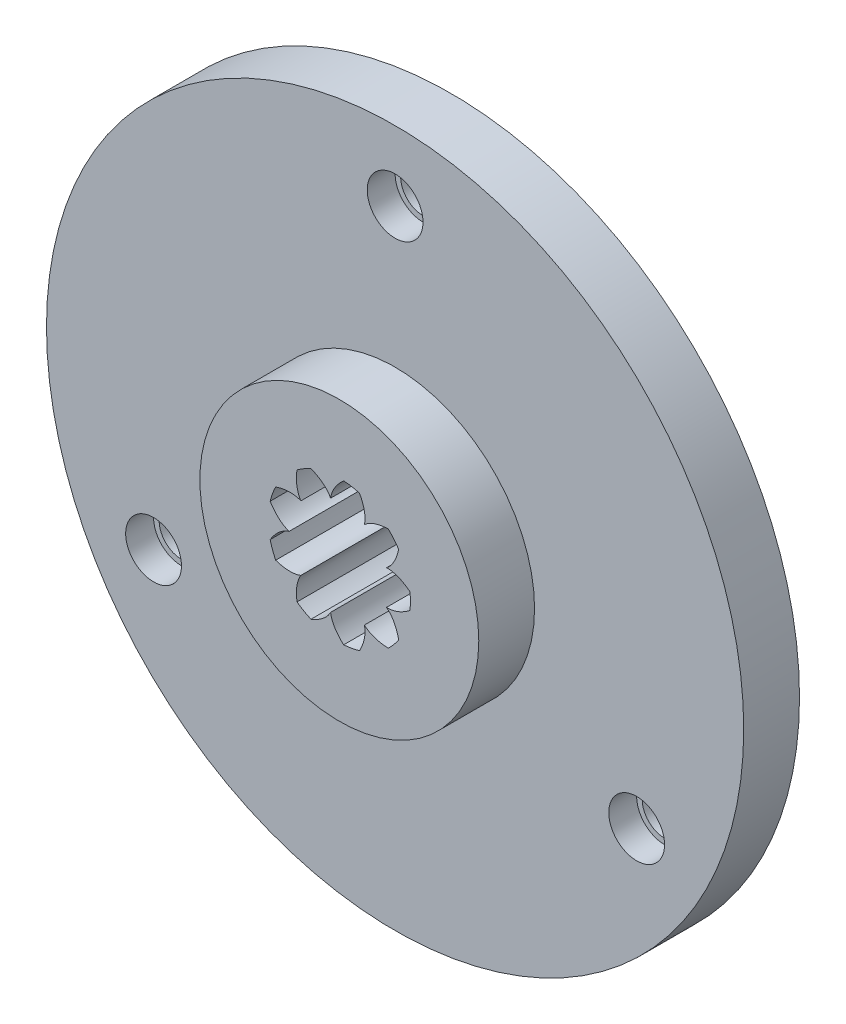
SolidWorks part; units mm, degrees
ref_plane "前视基准面" through (0, 0, 0) normal (0, 0, 1) x (1, 0, 0)
ref_plane "上视基准面" through (0, 0, 0) normal (0, 1, 0) x (1, 0, 0)
ref_plane "右视基准面" through (0, 0, 0) normal (1, 0, 0) x (0, 0, -1)
other "Configuration Table"
sketch "草图1" plane through (0, 0, 0) normal (0, 0, 1) x (1, 0, 0)
  line L0 (0, 0) -> (1.6914, 0.6156) construction
  line L1 (0, 0) -> (1.5832, 0.5954)
  line L2 (0, 0) -> (1.5832, -0.5954)
  line L3 (0, 0) -> (1.6914, -0.6156) construction
  line L4 (0, 0) -> (2.55, 0) construction
  line L5 (1.6914, 0.6156) -> (1.6914, -0.6156) construction
  circle A0 centre (0, 0) radius 1.65
  circle A1 centre (0, 0) radius 2.55
  circle A2 centre (0, 0) radius 1.6914 construction
  circle A3 centre (0, 0) radius 1.8 construction
  circle A4 centre (0, 0) radius 3
  spline S0 degree 4 poles (1.5832, 0.5954) (1.5953, 0.5999) (1.6299, 0.61) (1.6985, 0.6188) (1.8107, 0.6176) (1.9542, 0.5935) (2.1323, 0.5368) (2.3288, 0.4397) (2.527, 0.3033) (2.7182, 0.1281) (2.8863, -0.0692) (3.0309, -0.2841) (3.1583, -0.5243) (3.284, -0.8365) (3.3855, -1.2255) (3.4358, -1.6902) (3.4119, -2.2085) (3.3126, -2.7182) (3.1474, -3.2089) (2.918, -3.6756) (2.6387, -4.1089) (2.3029, -4.5102) (1.9385, -4.866) (1.5141, -5.1906) (1.1742, -5.4065) (0.7714, -5.6132) (0.5343, -5.7151) (0.2601, -5.8236) (0.1183, -5.8645) (-0.005, -5.9055) (-0.0434, -5.9147) (-0.0704, -5.9226) (-0.0848, -5.927) knots 0 0 0 0 0 0.005604 0.015718 0.02996 0.048734 0.068727 0.096889 0.125051 0.153212 0.181374 0.209535 0.237696 0.271429 0.327752 0.384075 0.440398 0.496721 0.553044 0.609367 0.66569 0.722013 0.778336 0.834659 0.890982 0.909091 0.954545 0.977273 0.988636 0.994318 1 1 1 1 1 construction
  spline S1 degree 4 poles (1.5832, 0.5954) (1.5953, 0.5999) (1.6299, 0.61) (1.6985, 0.6188) (1.8107, 0.6176) (1.9542, 0.5935) (2.1323, 0.5368) (2.3288, 0.4397) (2.527, 0.3033) (2.7182, 0.1281) (2.8863, -0.0692) (3.0309, -0.2841) (3.1583, -0.5243) (3.284, -0.8365) (3.3855, -1.2255) (3.4358, -1.6902) (3.4119, -2.2085) (3.3126, -2.7182) (3.1474, -3.2089) (2.918, -3.6756) (2.6387, -4.1089) (2.3029, -4.5102) (1.9385, -4.866) (1.5141, -5.1906) (1.1742, -5.4065) (0.8753, -5.5599) (0.734, -5.626) (0.6996, -5.6416) knots 0 0 0 0 0 0.005604 0.015718 0.02996 0.048734 0.068727 0.096889 0.125051 0.153212 0.181374 0.209535 0.237696 0.271429 0.327752 0.384075 0.440398 0.496721 0.553044 0.609367 0.66569 0.722013 0.778336 0.834659 0.890982 0.909091 0.909091 0.909091 0.909091 0.909091
  spline S2 degree 4 poles (1.5832, -0.5954) (1.5953, -0.5999) (1.6299, -0.61) (1.6985, -0.6188) (1.8107, -0.6176) (1.9542, -0.5935) (2.1323, -0.5368) (2.3288, -0.4397) (2.527, -0.3033) (2.7182, -0.1281) (2.8863, 0.0692) (3.0309, 0.2841) (3.1583, 0.5243) (3.284, 0.8365) (3.3855, 1.2255) (3.4358, 1.6902) (3.4119, 2.2085) (3.3126, 2.7182) (3.1474, 3.2089) (2.918, 3.6756) (2.6387, 4.1089) (2.3029, 4.5102) (1.9385, 4.866) (1.5141, 5.1906) (1.1742, 5.4065) (0.7714, 5.6132) (0.5343, 5.7151) (0.2601, 5.8236) (0.1183, 5.8645) (-0.005, 5.9055) (-0.0434, 5.9147) (-0.0704, 5.9226) (-0.0848, 5.927) knots 0 0 0 0 0 0.005604 0.015718 0.02996 0.048734 0.068727 0.096889 0.125051 0.153212 0.181374 0.209535 0.237696 0.271429 0.327752 0.384075 0.440398 0.496721 0.553044 0.609367 0.66569 0.722013 0.778336 0.834659 0.890982 0.909091 0.954545 0.977273 0.988636 0.994318 1 1 1 1 1 construction
  spline S3 degree 4 poles (1.5832, -0.5954) (1.5953, -0.5999) (1.6299, -0.61) (1.6985, -0.6188) (1.8107, -0.6176) (1.9542, -0.5935) (2.1323, -0.5368) (2.3288, -0.4397) (2.527, -0.3033) (2.7182, -0.1281) (2.8863, 0.0692) (3.0309, 0.2841) (3.1583, 0.5243) (3.284, 0.8365) (3.3855, 1.2255) (3.4358, 1.6902) (3.4119, 2.2085) (3.3126, 2.7182) (3.1474, 3.2089) (2.918, 3.6756) (2.6387, 4.1089) (2.3029, 4.5102) (1.9385, 4.866) (1.5141, 5.1906) (1.1742, 5.4065) (0.8753, 5.5599) (0.734, 5.626) (0.6996, 5.6416) knots 0 0 0 0 0 0.005604 0.015718 0.02996 0.048734 0.068727 0.096889 0.125051 0.153212 0.181374 0.209535 0.237696 0.271429 0.327752 0.384075 0.440398 0.496721 0.553044 0.609367 0.66569 0.722013 0.778336 0.834659 0.890982 0.909091 0.909091 0.909091 0.909091 0.909091
  point P16 (1.6914, 0)
  dimension "内啮合齿顶圆直径" = 3.3
  dimension "内啮合分度圆直径" = 3.6
  dimension "内啮合基圆直径" = 3.3829
  dimension "内啮合齿根圆直径" = 5.1
  dimension "外径" = 6
  dimension "渐开线镜像线夹角" = 20
extrude "凸台-拉伸1" add sketch "草图1" along normal blind 4 contours A4 | A0
extrude "切除-拉伸2" cut sketch "草图1<3>" along normal through all contours A0 S3 A1 S1 region at (2.0287, 0, 0)
sketch "草图1<3>" plane through (0, 0, 0) normal (0, 0, 1) x (1, 0, 0) same geometry as "草图1"
pattern_circular "阵列(圆周)1" count 9 over 360 about axis through (0, 0, 4) along (0, 0, 1) of "切除-拉伸2"
sketch "草图2" plane through (0, 0, 0) normal (0, 0, -1) x (-1, 0, 0)
  circle A0 centre (0, 0) radius 3
  circle A1 centre (0, 0) radius 3 construction
  circle A2 centre (0, 0) radius 5
  dimension "D1" = 10
extrude "凸台-拉伸2" add sketch "草图2" against normal up to surface (4 mm away) contours A2 | A0 up to face at (3, 0, 4)
sketch "草图3" plane through (0, 0, 0) normal (0, 0, 1) x (1, 0, 0)
  circle A0 centre (0, 10) radius 1
  circle A1 centre (0, 10) radius 0.8
  circle A2 centre (0, 0) radius 12.5
  circle A3 centre (8.6603, -5) radius 0.8
  circle A4 centre (8.6603, -5) radius 1
  circle A5 centre (-8.6603, -5) radius 0.8
  circle A6 centre (-8.6603, -5) radius 1
  circle A7 centre (0, 0) radius 5
  circle A10 centre (0, 0) radius 5 construction
  point P14 (0, 0)
  dimension "D4" = 1.6
  dimension "D5" = 2
  dimension "D1" = 25
  dimension "D2" = 3
  dimension "D3" = 10
extrude "凸台-拉伸4" add sketch "草图3" along normal blind 2 contours A2 | A5 | A3 | A1 | A7
extrude "切除-拉伸3" cut sketch "草图3<3>" against normal offset from surface (1 mm away) 1 from surface contours A0 | A4 | A6 up to face at (0, 0, 0) starting at face at (0.8, 10, 2)
sketch "草图3<3>" plane through (0, 0, 0) normal (0, 0, 1) x (1, 0, 0) same geometry as "草图3"
equation "\"m\"= 0.4'模数"
equation "\"z1\"= 9'外啮合齿轮数"
equation "\"a\"= 20度'压力角"
equation "\"z2\"= 9'内啮合齿轮数"
equation "\"hax\"= 1'齿顶高系数"
equation "\"cx\"= 0.25'顶隙系数"
equation "\"ha\"= \"hax\" * \"m\"'齿顶高"
equation "\"hf\"= ( \"hax\" + \"cx\" ) * \"m\"'齿根高"
equation "\"d1\"= \"m\" * \"z1\"'外啮合分度圆直径"
equation "\"da1\"= ( \"z1\" + 2 ) * \"m\"'外啮合齿顶圆直径"
equation "\"df1\"= \"d1\" - 2 * \"hf\"'外啮合齿根圆直径"
equation "\"db1\"= \"d1\" * cos ( \"a\" )'外啮合基圆直径"
equation "\"p\"= \"m\" * PI'齿距"
equation "\"d2\"= \"m\" * \"z2\"'内啮合分度圆直径"
equation "\"db2\"= \"d2\" * cos ( \"a\" )'内啮合基圆直径"
equation "\"da2\"= ( \"z2\" - 2 ) * \"m\"'内啮合齿顶圆直径"
equation "\"df2\"= \"d2\" + 2 * \"hf\"'内啮合齿根圆直径"
equation "\"内啮合齿顶圆直径@草图1\" = \"da2\" + 1 * \"hf\""
equation "\"内啮合齿根圆直径@草图1\" = \"df2\" + 1 * \"hf\""
equation "\"内啮合分度圆直径@草图1\"= \"d2\""
equation "\"内啮合基圆直径@草图1\"= \"db2\""
equation "\"渐开线镜像线夹角@草图1\"= 360度 / 4 / \"z2\" + 360度 / 4 / \"z2\""
equation "\"do\"= IIF ( \"edo\" >= ( \"df2\" + 1 ) , \"edo\" , ( \"df2\" + 1 ) )'外圈直径"
equation "\"h\"= 4'厚度"
equation "\"外径@草图1\"= \"do\""
equation "\"厚度@凸台-拉伸1\"= \"h\""
equation "\"内啮合齿轮数@阵列(圆周)1\"= \"z2\""
equation "\"edo\"= 6'期望的外圈直径"
